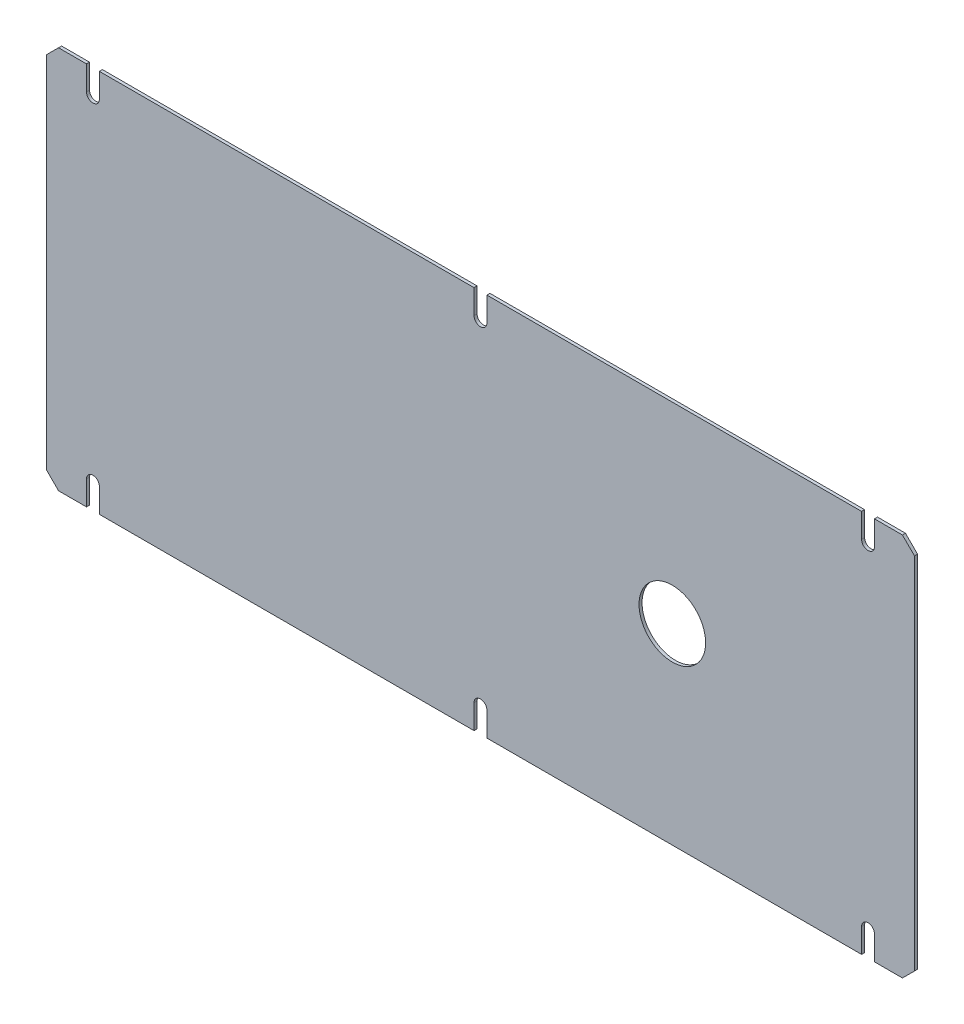
SolidWorks part; units mm, degrees
note: '?' marks a value the reader was unsure of.
material "PE High Density"
ref_plane "Front" through (0, 0, 0) normal (0, 0, 1) x (1, 0, 0)
ref_plane "Top" through (0, 0, 0) normal (0, 1, 0) x (1, 0, 0)
ref_plane "Right" through (0, 0, 0) normal (1, 0, 0) x (0, 0, -1)
ref_axis "Axis1" through (0, 0, 55) along (0, 0, -1)?
sketch "Sketch1" plane through (0, 0, 0) normal (0, 0, 1) x (1, 0, 0)
  line L1 (-227.584, 100.584) -> (227.584, 100.584)
  line L2 (-227.584, 100.584) -> (-227.584, -100.584)
  line L3 (-227.584, -100.584) -> (227.584, -100.584)
  line L4 (227.584, 100.584) -> (227.584, -100.584)
  line L5 (-227.584, 100.584) -> (227.584, -100.584) construction
  line L6 (-227.584, -100.584) -> (227.584, 100.584) construction
  point P0 (0, 0)
  dimension "D1" = 201.168
  dimension "D2" = 455.168
extrude "Boss-Extrude1" add sketch "Sketch1" along normal blind 1.5875
hole_wizard "1/4 Clearance Hole1" positions "Sketch2" profile "Sketch3" hole size "1/4" standard "ANSI Inch" end condition up to next
sketch "Sketch2" plane through (0, 0, 1.5875) normal (0, 0, 1) x (1, 0, 0)
  line L2 (-214.884, 87.884) -> (214.884, 87.884) construction
  line L3 (-214.884, 87.884) -> (-214.884, -87.884) construction
  line L4 (-214.884, -87.884) -> (214.884, -87.884) construction
  line L5 (214.884, 87.884) -> (214.884, -87.884) construction
  line L6 (-214.884, 87.884) -> (214.884, -87.884) construction
  line L7 (-214.884, -87.884) -> (214.884, 87.884) construction
  line L8 (-227.584, 100.584) -> (-227.584, -100.584) construction
  line L9 (227.584, 100.584) -> (-227.584, 100.584) construction
  line L10 (-227.584, -100.584) -> (227.584, -100.584) construction
  line L11 (227.584, -100.584) -> (227.584, 100.584) construction
  line L12 (-214.884, 0) -> (214.884, 0) construction
  line L14 (0, 87.884) -> (0, -87.884) construction
  line L15 (-203.2, 87.884) -> (-203.2, -87.884) construction
  line L17 (203.2, 87.884) -> (203.2, -87.884) construction
  point P0 (-203.2, 87.884)
  point P2 (203.2, 87.884)
  point P8 (-203.2, -87.884)
  point P10 (203.2, -87.884)
  point P249 (-214.884, 0)
  dimension "D1" = 12.7
  dimension "D2" = 12.7
  dimension "D3" = 12.7
  dimension "D4" = 12.7
  dimension "D5" = 406.4
sketch "Sketch3" plane through (-203.2, 87.884, 1.5875) normal (1, 0, 0) x (0, -1, 0)
  line L0 (0, 0) -> (0, 1.5875)
  line L1 (0, 1.5875) -> (3.3782, 1.5875)
  line L2 (3.3782, 1.5875) -> (3.3782, 0)
  line L5 (3.3782, 0) -> (0, 0)
  line L11 (0, -6.35) -> (0, 107.95) construction
  dimension "Thru Hole Dia." = 6.7564
  dimension "Thru Hole Depth" = 1.5875
sketch "Sketch4" plane through (0, 0, 1.5875) normal (0, 0, 1) x (1, 0, 0)
  line L0 (-227.584, 0) -> (227.584, 0) construction
  line L1 (-227.584, 100.584) -> (-227.584, -100.584) construction
  line L2 (227.584, -100.584) -> (227.584, 100.584) construction
  circle A0 centre (100.584, 0) radius 17.4625
  dimension "D1" = 34.925
  dimension "D2" = 127
other "Cosmetic Pattern1" parameters "D10"=8, "D5"=0, "D6"=0, "D4"=14.8256, "D9"=0
extrude "Cut-Extrude1" cut sketch "Sketch4" against normal up to next
hole_wizard "1/4 Clearance Hole2" positions "Sketch5" profile "Sketch6" hole size "1/4" standard "ANSI Inch" end condition up to next
sketch "Sketch5" plane through (0, 0, 1.5875) normal (0, 0, 1) x (1, 0, 0)
  line L0 (-203.2, 87.884) -> (203.2, 87.884) construction
  line L2 (-203.2, -87.884) -> (203.2, -87.884) construction
  point P0 (0, -87.884)
  point P2 (0, 87.884)
sketch "Sketch6" plane through (0, -87.884, 1.5875) normal (1, 0, 0) x (0, -1, 0)
  line L0 (0, 0) -> (0, 1.5875)
  line L1 (0, 1.5875) -> (3.3782, 1.5875)
  line L2 (3.3782, 1.5875) -> (3.3782, 0)
  line L5 (3.3782, 0) -> (0, 0)
  line L11 (0, -6.35) -> (0, 107.95) construction
  dimension "Thru Hole Dia." = 6.7564
  dimension "Thru Hole Depth" = 1.5875
sketch "Sketch7" plane through (0, 0, 1.5875) normal (0, 0, 1) x (1, 0, 0)
  line L0 (-206.5782, -87.884) -> (206.5782, -87.884) construction
  line L2 (-206.5782, -87.884) -> (-199.8218, -87.884)
  line L3 (-206.5782, -87.884) -> (-206.5782, -102.362)
  line L4 (-206.5782, -102.362) -> (-199.8218, -102.362)
  line L5 (-199.8218, -87.884) -> (-199.8218, -102.362)
  line L6 (-206.5782, -87.884) -> (-199.8218, -102.362) construction
  line L7 (-206.5782, -102.362) -> (-199.8218, -87.884) construction
  line L8 (-3.3782, -87.884) -> (3.3782, -87.884)
  line L9 (-3.3782, -87.884) -> (-3.3782, -102.362)
  line L10 (-3.3782, -102.362) -> (3.3782, -102.362)
  line L11 (3.3782, -87.884) -> (3.3782, -102.362)
  line L12 (-3.3782, -87.884) -> (3.3782, -102.362) construction
  line L13 (-3.3782, -102.362) -> (3.3782, -87.884) construction
  line L14 (206.5782, -87.884) -> (199.8218, -87.884)
  line L15 (206.5782, -87.884) -> (206.5782, -102.362)
  line L16 (206.5782, -102.362) -> (199.8218, -102.362)
  line L17 (199.8218, -87.884) -> (199.8218, -102.362)
  line L18 (206.5782, -87.884) -> (199.8218, -102.362) construction
  line L19 (206.5782, -102.362) -> (199.8218, -87.884) construction
  circle A0 centre (-203.2, -87.884) radius 3.3782 construction
  circle A1 centre (203.2, -87.884) radius 3.3782 construction
  circle A2 centre (0, -87.884) radius 3.3782 construction
  point P10 (-203.2, -95.123)
  point P15 (0, -95.123)
  point P21 (203.2, -95.123)
  dimension "D1" = 14.478
extrude "Cut-Extrude2" cut sketch "Sketch7" against normal up to next
mirror "Mirror1" about plane through (0, 0, 0) normal (0, 1, 0) of "Cut-Extrude2"
chamfer "Chamfer1" distance 6.35 angle 45 4 edges at (-227.584, -100.584, 0.7937) (-227.584, 100.584, 0.7937) (227.584, -100.584, 0.7937) (227.584, 100.584, 0.7937)
